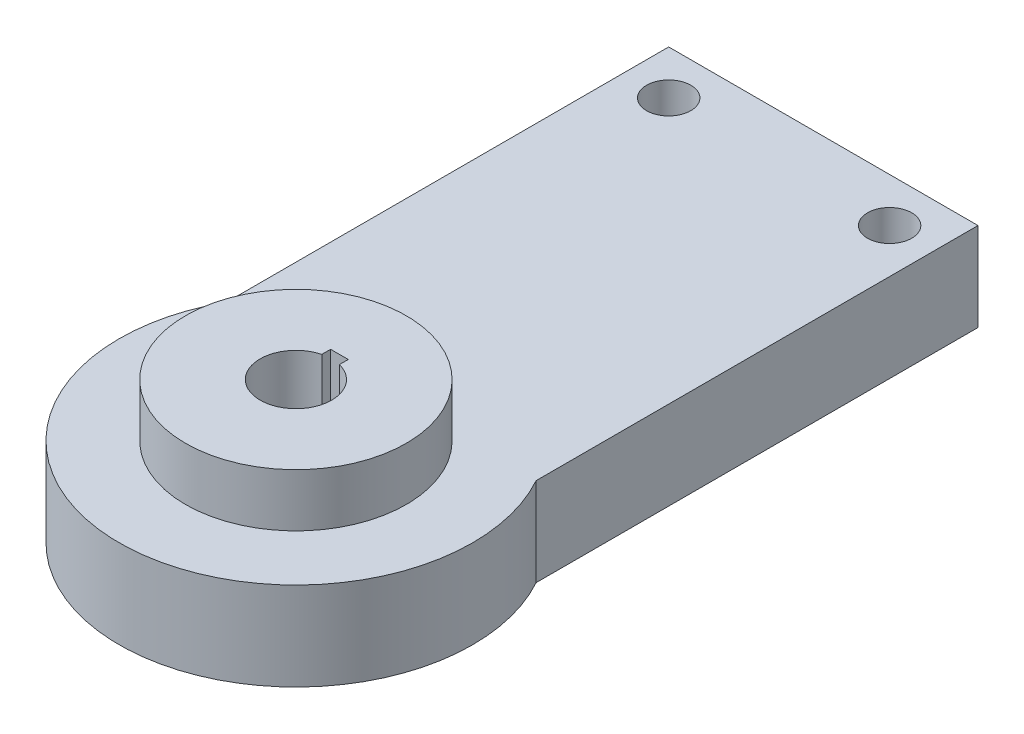
SolidWorks part; units mm, degrees
ref_plane "Front Plane" through (0, 0, 0) normal (0, 0, 1) x (1, 0, 0)
ref_plane "Top Plane" through (0, 0, 0) normal (0, 1, 0) x (1, 0, 0)
ref_plane "Right Plane" through (0, 0, 0) normal (1, 0, 0) x (0, 0, -1)
sketch "Sketch1" plane through (0, 0, 0) normal (0, 1, 0) x (1, 0, 0)
  circle A21 centre (0, 0) radius 20
  dimension "D1" = 40
extrude "Boss-Extrude1" add sketch "Sketch1" along normal blind 10
sketch "Sketch2" plane through (0, 10, 0) normal (0, 1, 0) x (1, 0, 0)
  line L0 (-1, 3.9246) -> (-1, 4.9246)
  line L1 (-1, 4.9246) -> (1, 4.9246)
  line L2 (1, 4.9246) -> (1, 3.9246)
  arc A1 (-1, 3.9246) -> (1, 3.9246) centre (0, 0) ccw
  point P4 (0, 4.9246)
  dimension "D1" = 8.1
  dimension "D2" = 1
  dimension "D3" = 2
extrude "Cut-Extrude1" cut sketch "Sketch2" against normal through all
sketch "Sketch3" plane through (0, 0, 0) normal (0, 1, 0) x (1, 0, 0)
  line L0 (-17.5, 59.6825) -> (-17.5, 9.6825)
  line L1 (-17.5, 59.6825) -> (17.5, 59.6825)
  line L2 (17.5, 59.6825) -> (17.5, 9.6825)
  circle A0 centre (0, 0) radius 20 construction
  arc A1 (17.5, 9.6825) -> (-17.5, 9.6825) centre (0, 0) ccw
  point P6 (0, 59.6825)
  point P9 (0, 20)
  dimension "D1" = 35
  dimension "D2" = 50
extrude "Boss-Extrude2" add sketch "Sketch3" along normal up to surface (10 mm away) up to face at (0, 10, -2.431)
sketch "Sketch5" plane through (0, 10, 0) normal (0, 1, 0) x (1, 0, 0)
  line L0 (17.5, 9.6825) -> (17.5, 59.6825) construction
  line L1 (-17.5, 59.6825) -> (17.5, 59.6825) construction
  line L2 (-17.5, 59.6825) -> (-17.5, 49.6825) construction
  line L3 (-17.5, 49.6825) -> (17.5, 49.6825) construction
  line L4 (17.5, 59.6825) -> (17.5, 49.6825) construction
  line L5 (-12.5, 54.6825) -> (12.5, 54.6825) construction
  circle A0 centre (-12.5, 54.6825) radius 2.5
  circle A1 centre (12.5, 54.6825) radius 2.5
  point P11 (0, 54.6825)
  point P14 (-17.5, 54.6825)
  dimension "D3" = 5
  dimension "D1" = 10
  dimension "D2" = 25
extrude "Cut-Extrude2" cut sketch "Sketch5" against normal through all
sketch "Sketch6" plane through (0, 10, 0) normal (0, 1, 0) x (1, 0, 0)
  line L0 (-1, 4.9246) -> (1, 4.9246)
  line L1 (1, 4.9246) -> (1, 3.9246)
  line L2 (1, 3.9246) -> (1, 4.9246) construction
  line L3 (-1, 4.9246) -> (-1, 3.9246)
  line L4 (-1, 4.9246) -> (-1, 3.9246) construction
  circle A0 centre (0, 0) radius 12.5
  arc A1 (-1, 3.9246) -> (1, 3.9246) centre (0, 0) ccw
  arc A2 (-1, 3.9246) -> (1, 3.9246) centre (0, 0) ccw construction
  dimension "D1" = 25
extrude "Boss-Extrude3" add sketch "Sketch6" along normal blind 6
